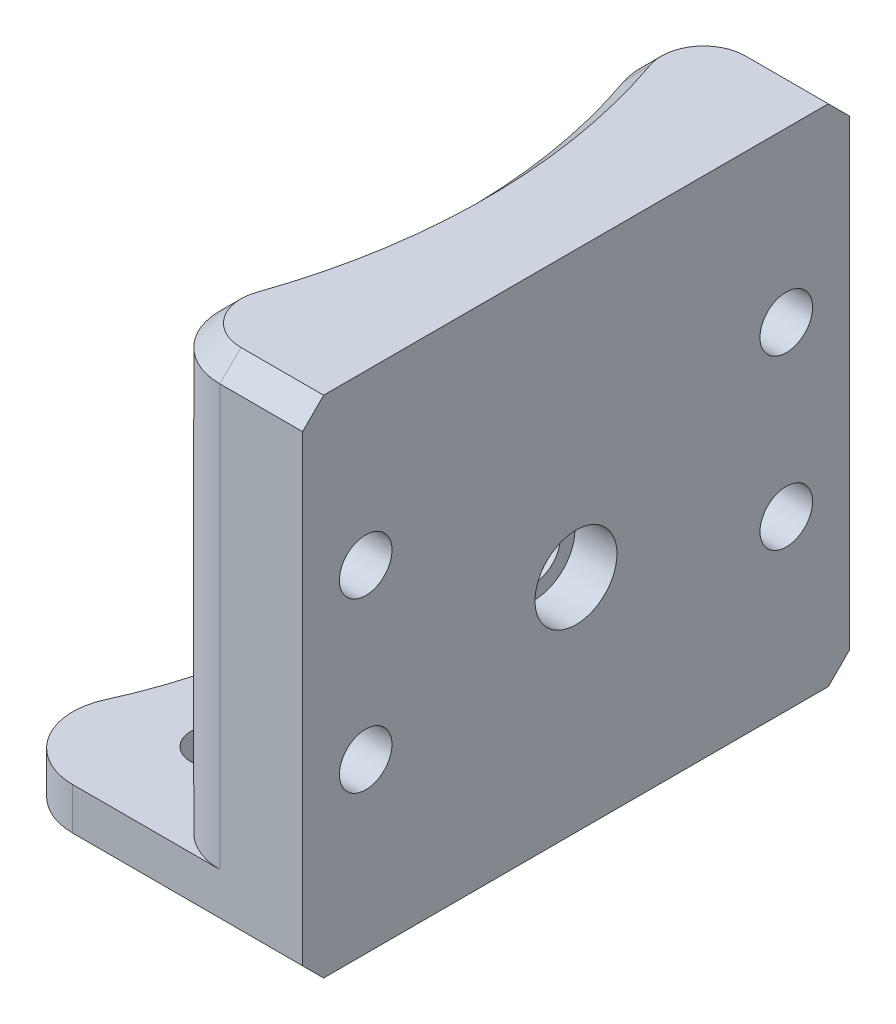
SolidWorks part; units mm, degrees
ref_plane "Спереди" through (0, 0, 0) normal (0, 0, 1) x (1, 0, 0)
ref_plane "Сверху" through (0, 0, 0) normal (0, 1, 0) x (1, 0, 0)
ref_plane "Справа" through (0, 0, 0) normal (1, 0, 0) x (0, 0, -1)
sketch "Эскиз1" plane through (0, 0, 0) normal (0, 1, 0) x (1, 0, 0)
  line L0 (23.6854, 8) -> (23.6854, -8) construction
  line L1 (16.4924, 13) -> (32.75, 13)
  line L2 (16.4924, 13) -> (16.4924, -13) construction
  line L3 (16.4924, -13) -> (32.75, -13)
  line L4 (32.75, 13) -> (32.75, -13)
  circle A0 centre (0, 0) radius 25 construction
  circle A2 centre (0, 0) radius 21
  circle A3 centre (23.6854, 8) radius 1.25
  circle A4 centre (23.6854, -8) radius 1.25
  dimension "D1" = 50
  dimension "D6" = 2.5
  dimension "D7" = 2.5
  dimension "D3" = 26
  dimension "D4" = 32.75
  dimension "D5" = 16
extrude "Бобышка-Вытянуть1" add sketch "Эскиз1" along normal blind 24 contours A2 L3 L4 L1 A4 A3 region at (26.1643, 0, 0)
sketch "Эскиз2" plane through (0, 24, 0) normal (0, 1, 0) x (1, 0, 0)
  circle A0 centre (0, 0) radius 25 construction
  circle A1 centre (0, 0) radius 27.5
  dimension "D1" = 2.5
extrude "Вырез-Вытянуть1" cut sketch "Эскиз2" against normal offset from surface (21 mm away) 3 up to face at (23.6854, 0, 9.25)
fillet "Скругление1" radius 3 4 edges at (24.2332, 13.5, 13) (24.2332, 13.5, -13) (16.4924, 1.5, -13) (16.4924, 1.5, 13)
sketch "Эскиз3" plane through (32.75, 0, 0) normal (1, 0, 0) x (0, 0, -1)
  line L0 (13, 0) -> (-13, 0) construction
  line L1 (-13, 12) -> (13, 12) construction
  line L2 (-10, 16) -> (-10, 8) construction
  line L3 (0, 0) -> (0, 24) construction
  line L4 (13, 24) -> (-13, 24) construction
  line L5 (-13, 24) -> (-13, 0) construction
  line L6 (13, 24) -> (13, 0) construction
  circle A0 centre (0, 10.5) radius 1.25
  circle A2 centre (-10, 16) radius 1.25
  circle A3 centre (-10, 8) radius 1.25
  circle A4 centre (10, 8) radius 1.25
  circle A5 centre (10, 16) radius 1.25
  point P4 (0, 0)
  point P17 (-13, 12)
  dimension "D1" = 2.5
  dimension "D3" = 2.5
  dimension "D2" = 10.5
  dimension "D4" = 8
  dimension "D5" = 20
extrude "Вырез-Вытянуть2" cut sketch "Эскиз3" against normal through all
chamfer "Фаска2" distance 1 angle 45 10 edges at (30.782, 24, -13) (26.3696, 24, -11.7391) (27.5, 24, 0) (30.782, 24, 13) (26.3696, 24, 11.7391) (27.2837, 0, -13) (19.2925, 0, -11.6202) (21, 0, 0) (19.2925, 0, 11.6202) (27.2837, 0, 13)
sketch "Эскиз4" plane through (0, 0, 0) normal (1, 0, 0) x (0, 0, -1)
  line L0 (-13, 12) -> (13, 12) construction
  line L1 (-7.85, 14.7587) -> (-7.85, 17.2413)
  line L2 (-7.85, 17.2413) -> (-10, 18.4826)
  line L3 (-10, 18.4826) -> (-12.15, 17.2413)
  line L4 (-12.15, 17.2413) -> (-12.15, 14.7587)
  line L5 (-12.15, 14.7587) -> (-10, 13.5174)
  line L6 (-10, 13.5174) -> (-7.85, 14.7587)
  line L7 (-13, 23) -> (-13, 1) construction
  line L8 (13, 23) -> (13, 1) construction
  line L9 (0, 24) -> (0, 0) construction
  line L10 (12, 24) -> (-12, 24) construction
  line L11 (12, 0) -> (-12, 0) construction
  line L12 (-10, 10.4826) -> (-7.85, 9.2413)
  line L13 (-12.15, 9.2413) -> (-10, 10.4826)
  line L14 (-12.15, 6.7587) -> (-12.15, 9.2413)
  line L15 (-10, 5.5174) -> (-12.15, 6.7587)
  line L16 (-7.85, 6.7587) -> (-10, 5.5174)
  line L17 (-7.85, 9.2413) -> (-7.85, 6.7587)
  line L18 (7.85, 9.2413) -> (7.85, 6.7587)
  line L19 (7.85, 6.7587) -> (10, 5.5174)
  line L20 (10, 5.5174) -> (12.15, 6.7587)
  line L21 (12.15, 6.7587) -> (12.15, 9.2413)
  line L22 (12.15, 9.2413) -> (10, 10.4826)
  line L23 (10, 10.4826) -> (7.85, 9.2413)
  line L24 (10, 13.5174) -> (7.85, 14.7587)
  line L25 (12.15, 14.7587) -> (10, 13.5174)
  line L26 (12.15, 17.2413) -> (12.15, 14.7587)
  line L27 (10, 18.4826) -> (12.15, 17.2413)
  line L28 (7.85, 17.2413) -> (10, 18.4826)
  line L29 (7.85, 14.7587) -> (7.85, 17.2413)
  circle A0 centre (-10, 16) radius 2.15 construction
  dimension "D1" = 4.3
extrude "Вырез-Вытянуть3" cut sketch "Эскиз4" along normal offset from surface (29.75 mm away) 3 up to face at (32.75, 16, -8.75)
sketch "Эскиз5" plane through (32.75, 0, 0) normal (1, 0, 0) x (0, 0, -1)
  circle A0 centre (0, 10.5) radius 1.95
  dimension "D1" = 3.9
extrude "Вырез-Вытянуть4" cut sketch "Эскиз5" against normal blind 2
sketch "Эскиз6" plane through (0, 0, 0) normal (0, -1, 0) x (1, 0, 0)
  circle A0 centre (23.6854, 8) radius 1.95
  circle A1 centre (23.6854, -8) radius 1.95
  dimension "D1" = 3.9
  dimension "D2" = 3.9
extrude "Вырез-Вытянуть5" cut sketch "Эскиз6" against normal blind 1
equation "\"motor_diameter\"= 30"
equation "\"mm_diameter\"= IIF ( \"motor_diameter\" < 34 , 41 , \"motor_diameter\" + 8 )"
equation "\"upper_shafts_diameter\"= 5"
equation "\"upper_shats_length\"= 180"
equation "\"upper_bearing_d1\"= 10"
equation "\"upper_bearing_d2\"= 5"
equation "\"upper_bearing_h\"= 15"
equation "\"lower_shafts_diameter\"= 5"
equation "\"lower_shafts_length\"= 180"
equation "\"lower_bearing_d1\"= 10"
equation "\"lower_bearing_d2\"= 5"
equation "\"lower_bearing_h\"= 15"
equation "\"print_offset\"= 0.5"
equation "\"bh_screws_d\"= 2"
equation "\"bh_screws_h\"= 20"
equation "\"bh_screws_hh_d\"= 3.4"
equation "\"bh_screws_hh_h\"= 2"
equation "\"bh_nut_d\"= 3.8"
equation "\"bh_nut_h\"= 2"
equation "\"motor_screws_d\"= 3"
equation "\"motor_screws_h\"= 16"
equation "\"motor_screws_hh_d\"= 5.5"
equation "\"motor_screws_hh_h\"= 3"
equation "\"plate_hole_distance\"= 25.4"
equation "\"plate_screws_d\"= 6.5"
equation "\"shafts_diameter\"= IIF ( \"mm_diameter\" < 42 , 42 + 8 , \"mm_diameter\" + 8 )"
equation "\"central_hole_diameter\"= 8"
equation "\"bh_thikness\"= 4"
equation "\"ends_screws_d\"= 4"
equation "\"ends_screws_h\"= 16"
equation "\"ends_screws_hh_d\"= 6.7"
equation "\"ends_screws_hh_h\"= 4.1"
equation "\"ends_nut_d\"= 6.8"
equation "\"ends_nut_h\"= 3"
equation "\"system_radius\" = ( \"shafts_diameter\" + 12 + \"bh_thikness\" / 2 ) / 2"
equation "\"encoder_distance\"= \"system_radius\" + 4"
equation "\"tape_position\"= \"encoder_distance\" - 2 + 3.9 + 1.7 / 2"
equation "\"D1@Эскиз1\"=\"shafts_diameter\""
equation "\"D2@Эскиз1\"=\"bh_thikness\""
equation "\"D4@Эскиз1\"=\"tape_position\"-6"
equation "\"D6@Эскиз1\"=\"bh_screws_d\"+\"print_offset\""
equation "\"D7@Эскиз1\"=\"D6@Эскиз1\""
equation "\"D1@Бобышка-Вытянуть1\"=\"upper_bearing_h\"+6+3"
equation "\"D1@Эскиз2\"=\"bh_thikness\"/2+\"print_offset\""
equation "\"D1@Эскиз3\"=\"bh_screws_d\"+\"print_offset\""
equation "\"D2@Эскиз3\"=\"upper_bearing_h\"/2+3"
equation "\"D3@Эскиз3\"=\"bh_screws_d\"+\"print_offset\""
equation "\"D1@Эскиз4\"=\"bh_nut_d\"+\"print_offset\""
equation "\"D1@Вырез-Вытянуть3\"=-1+12-8"
equation "\"D1@Эскиз5\"=\"bh_screws_hh_d\"+\"print_offset\""
equation "\"D1@Вырез-Вытянуть4\"=\"bh_screws_hh_h\""
equation "\"D1@Эскиз6\"=\"bh_screws_hh_d\"+\"print_offset\""
equation "\"D2@Эскиз6\"=\"D1@Эскиз6\""
equation "\"ft_sensor_d1\" = 9.8"
equation "\"ft_sensor_d2\"= 24.9"
equation "\"ft_sensor_h\"= 7"
equation "\"carbon_pipe_d\"= 14"
